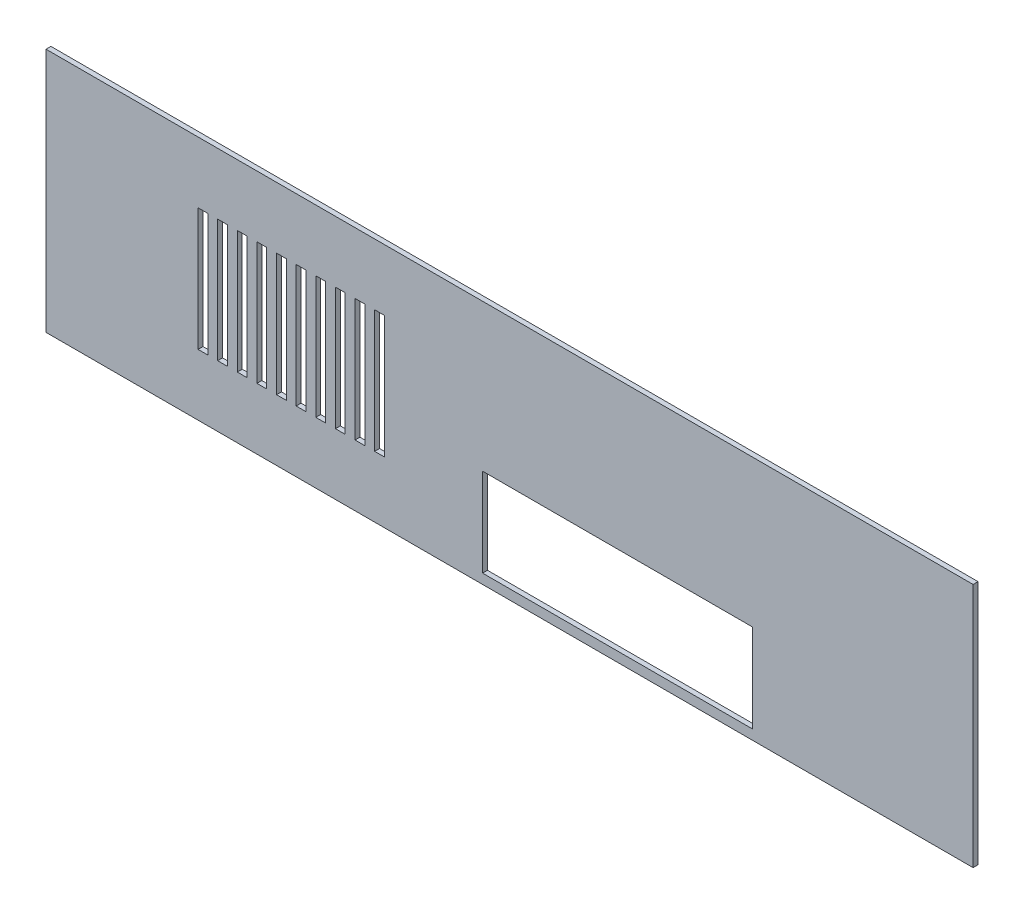
SolidWorks part; units mm, degrees
ref_plane "Front Plane" through (0, 0, 0) normal (0, 0, 1) x (1, 0, 0)
ref_plane "Top Plane" through (0, 0, 0) normal (0, 1, 0) x (1, 0, 0)
ref_plane "Right Plane" through (0, 0, 0) normal (1, 0, 0) x (0, 0, -1)
sketch "Sketch1" plane through (0, 0, 0) normal (0, 0, 1) x (1, 0, 0)
  line L1 (-61.6344, 41.198) -> (127.3656, 41.198)
  line L2 (-61.6344, 41.198) -> (-61.6344, -8.802)
  line L3 (-61.6344, -8.802) -> (127.3656, -8.802)
  line L4 (127.3656, 41.198) -> (127.3656, -8.802)
  dimension "D1" = 50
  dimension "D2" = 189
extrude "Boss-Extrude1" add sketch "Sketch1" along normal blind 1
sketch "Sketch2" plane through (0, 0, 1) normal (0, 0, 1) x (1, 0, 0)
  line L0 (-61.6344, -8.802) -> (127.3656, -8.802) construction
  line L1 (27.3656, 11.198) -> (82.3656, 11.198)
  line L2 (27.3656, 11.198) -> (27.3656, -6.802)
  line L3 (27.3656, -6.802) -> (82.3656, -6.802)
  line L4 (82.3656, 11.198) -> (82.3656, -6.802)
  line L5 (127.3656, -8.802) -> (127.3656, 41.198) construction
  dimension "D1" = 55
  dimension "D2" = 18
  dimension "D3" = 2
  dimension "D4" = 45
extrude "Cut-Extrude1" cut sketch "Sketch2" against normal through all
sketch "Sketch3" plane through (0, 0, 0) normal (0, 0, -1) x (-1, 0, 0)
  line L1 (-7.3656, 28.698) -> (-5.3656, 28.698)
  line L2 (-7.3656, 28.698) -> (-7.3656, 3.698)
  line L3 (-7.3656, 3.698) -> (-5.3656, 3.698)
  line L4 (-5.3656, 28.698) -> (-5.3656, 3.698)
  line L6 (61.6344, -8.802) -> (-127.3656, -8.802) construction
  line L9 (-27.3656, 11.198) -> (-27.3656, -6.802) construction
  line L10 (-3.3656, 28.698) -> (-1.3656, 28.698)
  line L11 (-3.3656, 28.698) -> (-3.3656, 3.698)
  line L12 (-3.3656, 3.698) -> (-1.3656, 3.698)
  line L13 (-1.3656, 28.698) -> (-1.3656, 3.698)
  line L14 (0.6344, 28.698) -> (2.6344, 28.698)
  line L15 (0.6344, 28.698) -> (0.6344, 3.698)
  line L16 (0.6344, 3.698) -> (2.6344, 3.698)
  line L17 (2.6344, 28.698) -> (2.6344, 3.698)
  line L18 (4.6344, 28.698) -> (6.6344, 28.698)
  line L19 (4.6344, 28.698) -> (4.6344, 3.698)
  line L20 (4.6344, 3.698) -> (6.6344, 3.698)
  line L21 (6.6344, 28.698) -> (6.6344, 3.698)
  line L22 (8.6344, 28.698) -> (10.6344, 28.698)
  line L23 (8.6344, 28.698) -> (8.6344, 3.698)
  line L24 (8.6344, 3.698) -> (10.6344, 3.698)
  line L25 (10.6344, 28.698) -> (10.6344, 3.698)
  line L26 (12.6344, 28.698) -> (14.6344, 28.698)
  line L27 (12.6344, 28.698) -> (12.6344, 3.698)
  line L28 (12.6344, 3.698) -> (14.6344, 3.698)
  line L29 (14.6344, 28.698) -> (14.6344, 3.698)
  line L30 (16.6344, 28.698) -> (18.6344, 28.698)
  line L31 (16.6344, 28.698) -> (16.6344, 3.698)
  line L32 (16.6344, 3.698) -> (18.6344, 3.698)
  line L33 (18.6344, 28.698) -> (18.6344, 3.698)
  line L34 (20.6344, 28.698) -> (22.6344, 28.698)
  line L35 (20.6344, 28.698) -> (20.6344, 3.698)
  line L36 (20.6344, 3.698) -> (22.6344, 3.698)
  line L37 (22.6344, 28.698) -> (22.6344, 3.698)
  line L38 (24.6344, 28.698) -> (26.6344, 28.698)
  line L39 (24.6344, 28.698) -> (24.6344, 3.698)
  line L40 (24.6344, 3.698) -> (26.6344, 3.698)
  line L41 (26.6344, 28.698) -> (26.6344, 3.698)
  line L42 (28.6344, 28.698) -> (30.6344, 28.698)
  line L43 (28.6344, 28.698) -> (28.6344, 3.698)
  line L44 (28.6344, 3.698) -> (30.6344, 3.698)
  line L45 (30.6344, 28.698) -> (30.6344, 3.698)
  dimension "D1" = 25
  dimension "D2" = 2
  dimension "D3" = 12.5
  dimension "D4" = 20
extrude "Cut-Extrude2" cut sketch "Sketch3" against normal through all
